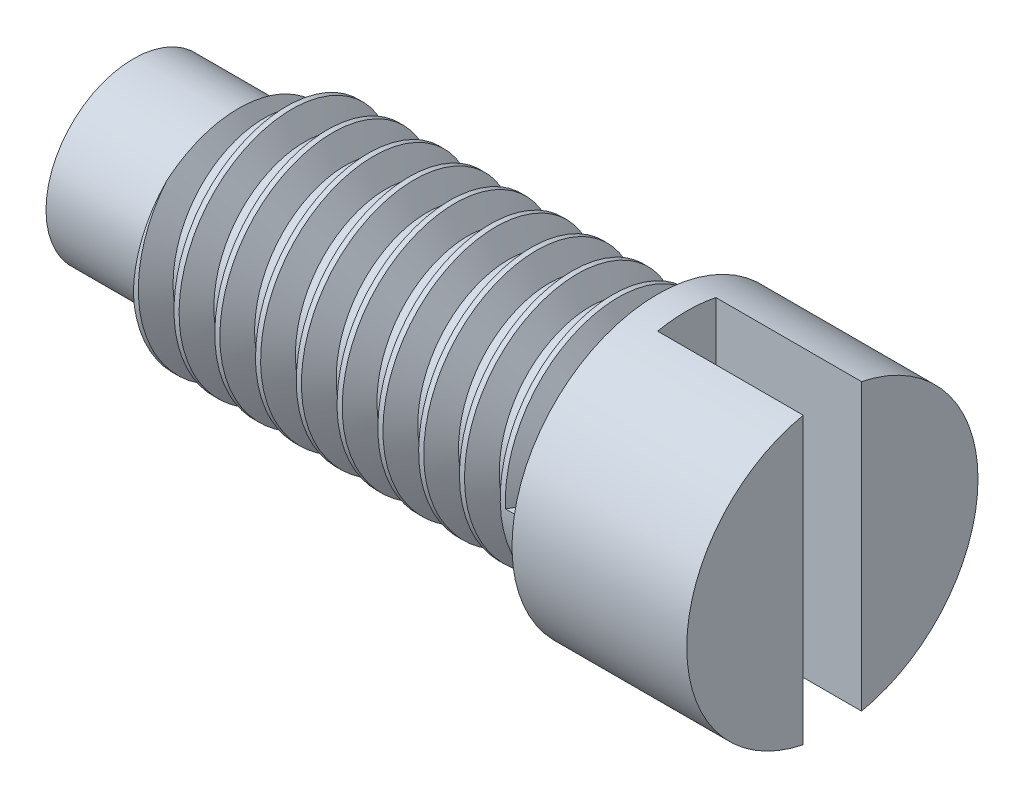
SolidWorks part; units mm, degrees
ref_plane "Front Plane" through (0, 0, 0) normal (0, 0, 1) x (1, 0, 0)
ref_plane "Top Plane" through (0, 0, 0) normal (0, 1, 0) x (1, 0, 0)
ref_plane "Right Plane" through (0, 0, 0) normal (1, 0, 0) x (0, 0, -1)
sketch "Sketch1" plane through (0, 0, 0) normal (0, 0, 1) x (1, 0, 0)
  line L0 (0, 0) -> (0, 1.5)
  line L1 (0, 1.5) -> (2, 1.5)
  line L2 (2, 1.5) -> (2, 2)
  line L3 (2, 2) -> (9, 2)
  line L4 (9, 2) -> (9, 2.5)
  line L5 (9, 2.5) -> (12, 2.5)
  line L6 (12, 2.5) -> (12, 0)
  line L7 (12, 0) -> (0, 0)
  dimension "D1" = 1.5
  dimension "D2" = 2
  dimension "D3" = 7
  dimension "D4" = 3
  dimension "D5" = 2
  dimension "D6" = 0.5
revolve "Revolve1" add sketch "Sketch1" angle 360 about L7
sketch "Sketch2" plane through (12, 0, 0) normal (1, 0, 0) x (0, 0, -1)
  line L1 (-0.5, -3.6696) -> (0.5, -3.6696)
  line L2 (-0.5, -3.6696) -> (-0.5, 3.6696)
  line L3 (-0.5, 3.6696) -> (0.5, 3.6696)
  line L4 (0.5, -3.6696) -> (0.5, 3.6696)
  line L5 (-0.5, -3.6696) -> (0.5, 3.6696) construction
  line L6 (-0.5, 3.6696) -> (0.5, -3.6696) construction
  point P0 (0, 0)
  dimension "D1" = 0.5
extrude "Cut-Extrude1" cut sketch "Sketch2" against normal blind 2.5
thread "Thread1" pitch 0.7 method cut profile "Thread Profile1" start angle 0, offset 0, length 7, pitch 0.7, diameter 4
ref_plane "Plane1" through (9, 0, 2) normal (0, -1, 0) x (0, 0, 1)
sketch "Thread Profile1" plane through (9, 0, 2) normal (0, -1, 0) x (0, 0, 1)
  line L0 (0, 0) -> (0, 0.7) construction
  line L11 (0, 0) -> (0, 0.6125)
  line L12 (0, 0.6125) -> (-0.3789, 0.3937)
  line L13 (-0.3789, 0.3937) -> (-0.3789, 0.2187)
  line L15 (-0.3789, 0.2187) -> (0, 0)
  line L17 (-0.3789, 0.3062) -> (0, 0.3062) construction
  point P2 (0, 0)
  dimension "Pitch" = 0.7
  dimension "Profile_Angle" = 60
  dimension "Profile_Land" = 0.175
  dimension "Profile_Height" = 0.3789
